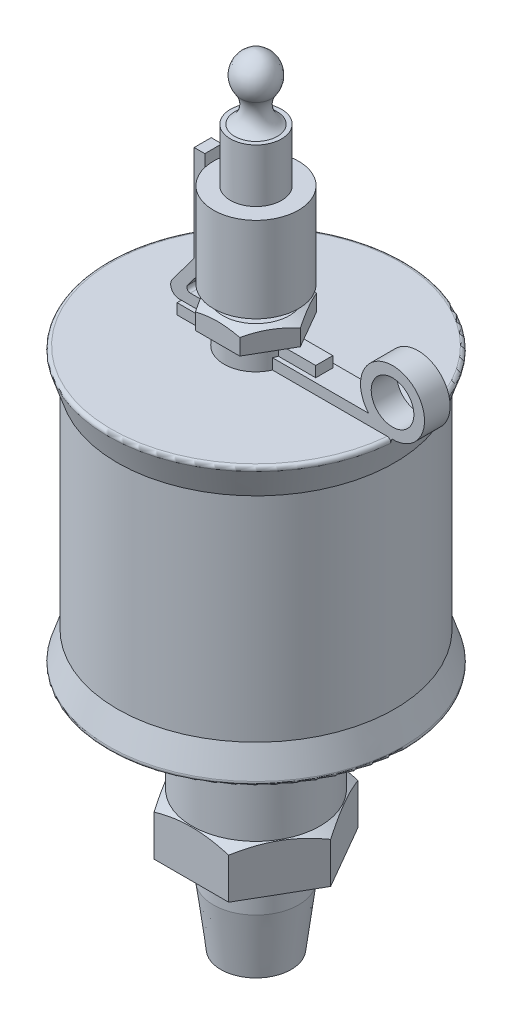
SolidWorks part; units mm, degrees
material "Plastic"
ref_plane "Front Plane" through (0, 0, 0) normal (0, 0, 1) x (1, 0, 0)
ref_plane "Top Plane" through (0, 0, 0) normal (0, 1, 0) x (1, 0, 0)
ref_plane "Right Plane" through (0, 0, 0) normal (1, 0, 0) x (0, 0, -1)
sketch "Sketch1" plane through (0, 0, 0) normal (0, 1, 0) x (1, 0, 0)
  circle A0 centre (0, 0) radius 22.225
  dimension "D1" = 44.45
extrude "Boss-Extrude1" add sketch "Sketch1" along normal mid plane 41.275
sketch "Sketch2" plane through (0, 0, 0) normal (0, 0, 1) x (1, 0, 0)
  line L0 (0, 21.5772) -> (0, -49978.4228) construction
  line L2 (-19.7921, 0) -> (49980.2079, 0) construction
  line L3 (20.6375, 15.875) -> (30.5336, 15.875)
  line L4 (20.6375, 15.875) -> (20.6375, -15.875)
  line L5 (20.6375, -15.875) -> (30.5336, -15.875)
  line L6 (30.5336, 15.875) -> (30.5336, -15.875)
  dimension "D1" = 41.275
  dimension "D2" = 31.75
revolve "Cut-Revolve1" cut sketch "Sketch2" angle 360 about L0
sketch "Sketch3" plane through (0, 0, 0) normal (0, 0, 1) x (1, 0, 0)
  line L0 (22.225, 20.6375) -> (20.6375, 15.875)
  line L1 (20.6375, 15.875) -> (22.225, 15.875)
  line L2 (22.225, 15.875) -> (22.225, 20.6375)
  line L3 (-22.6593, 0) -> (49977.3407, 0) construction
  line L5 (20.6375, -15.875) -> (22.225, -15.875)
  line L6 (22.225, -15.875) -> (22.225, -20.6375)
  line L7 (22.225, -20.6375) -> (20.6375, -15.875)
  line L8 (0, 12.3736) -> (0, -49987.6264) construction
revolve "Cut-Revolve2" cut sketch "Sketch3" angle 360 about L8
sketch "Sketch4" plane through (0, 0, 0) normal (0, 0, 1) x (1, 0, 0)
  line L0 (-10.3187, -20.6375) -> (0, -20.6375)
  line L1 (-22.225, -20.6375) -> (22.225, -20.6375) construction
  line L3 (0, -26.9875) -> (-10.3187, -26.9875)
  line L4 (-10.3187, -26.9875) -> (-10.3187, -20.6375)
  line L5 (0, 4.8841) -> (0, -49995.1159) construction
  line L7 (0, -20.6375) -> (0, -26.9875)
  dimension "D1" = 6.35
  dimension "D2" = 20.6375
revolve "Revolve2" add sketch "Sketch4" angle 360 about L5
sketch "Sketch5" plane through (0, 0, 0) normal (0, 0, 1) x (1, 0, 0)
  line L0 (-9.525, -26.9875) -> (-9.525, -36.5125)
  line L1 (-10.3187, -26.9875) -> (10.3187, -26.9875) construction
  line L2 (-9.525, -36.5125) -> (0, -36.5125)
  line L3 (0, -36.5125) -> (0, -26.9875) construction
  line L4 (0, -26.9875) -> (-9.525, -26.9875)
  line L5 (0, -36.5125) -> (0, -26.9875)
  dimension "D1" = 19.05
  dimension "D2" = 9.525
revolve "Revolve3" add sketch "Sketch5" angle 360 about L3
sketch "Sketch6" plane through (0, -36.5125, 0) normal (0, -1, 0) x (1, 0, 0)
  line L1 (11.1125, 0) -> (5.5562, 9.6237)
  line L2 (5.5562, 9.6237) -> (-5.5563, 9.6237)
  line L3 (-5.5563, 9.6237) -> (-11.1125, 0)
  line L4 (-11.1125, 0) -> (-5.5563, -9.6237)
  line L5 (-5.5563, -9.6237) -> (5.5562, -9.6237)
  line L6 (5.5562, -9.6237) -> (11.1125, 0)
  circle A0 centre (0, 0) radius 9.6237 construction
  dimension "D1" = 11.1125
extrude "Boss-Extrude2" add sketch "Sketch6" along normal blind 6.985
sketch "Sketch11" plane through (0, 0, 0) normal (0, 0, 1) x (1, 0, 0)
  line L0 (9.525, -36.5125) -> (11.1125, -37.429)
  line L1 (11.1125, -36.5125) -> (5.5562, -36.5125) construction
  line L2 (11.1125, -43.4975) -> (11.1125, -36.5125) construction
  line L3 (11.1125, -37.429) -> (11.1125, -36.5125)
  line L4 (11.1125, -36.5125) -> (9.525, -36.5125)
  line L5 (0, -29.1033) -> (0, -50029.1033) construction
  dimension "D1" = 1.5875
  dimension "D2" = 30
revolve "Cut-Revolve4" cut sketch "Sketch11" angle 360 about L5
sketch "Sketch12" plane through (0, 0, 0) normal (0, 0, 1) x (1, 0, 0)
  line L0 (0, -43.4975) -> (6.35, -43.4975)
  line L1 (5.5562, -43.4975) -> (-5.5563, -43.4975) construction
  line L2 (6.35, -43.4975) -> (6.35, -48.26)
  line L3 (6.35, -48.26) -> (0, -48.26)
  line L4 (0, -24.4475) -> (0, 24.4475) construction
  line L5 (0, -48.26) -> (0, -43.4975) construction
  line L6 (0, -43.4975) -> (0, -48.26)
  dimension "D1" = 12.7
  dimension "D2" = 4.7625
revolve "Revolve4" add sketch "Sketch12" angle 360 about L5
sketch "Sketch13" plane through (0, 0, 0) normal (0, 0, 1) x (1, 0, 0)
  line L0 (0, -57.15) -> (5.2387, -57.15)
  line L1 (5.2387, -57.15) -> (6.35, -48.26)
  line L2 (6.35, -48.26) -> (0, -48.26)
  line L3 (-6.35, -48.26) -> (6.35, -48.26) construction
  line L4 (0, -48.26) -> (0, -57.15) construction
  line L5 (0, -57.15) -> (0, -48.26)
  dimension "D1" = 10.4775
  dimension "D2" = 8.89
revolve "Revolve5" add sketch "Sketch13" angle 360 about L4
sketch "Sketch16" plane through (0, 0, 0) normal (0, 0, 1) x (1, 0, 0)
  line L0 (-9.8425, 20.6375) -> (22.225, 20.6375)
  line L1 (22.225, 20.6375) -> (-22.225, 20.6375) construction
  line L2 (0, 15.9486) -> (0, 50015.9486) construction
  line L4 (-9.8425, 20.6375) -> (-9.8425, 22.225)
  line L5 (-9.8425, 22.225) -> (18.6752, 22.225)
  arc A0 (22.225, 20.6375) -> (18.6752, 22.225) centre (22.225, 25.4) ccw
  circle A1 centre (22.225, 25.4) radius 3.175
  dimension "D3" = 9.525
  dimension "D4" = 1.5875
  dimension "D1" = 9.8425
  dimension "D2" = 22.225
  dimension "D5" = 1.5875
extrude "Boss-Extrude3" add sketch "Sketch16" along normal mid plane 3.81
sketch "Sketch17" plane through (0, 0, 0) normal (0, 0, 1) x (1, 0, 0)
  line L0 (0, 31.4144) -> (0, -49968.5856) construction
  line L1 (-11.176, 24.257) -> (-7.9375, 28.575)
  line L2 (0, 22.225) -> (10.16, 22.225)
  line L3 (18.6752, 22.225) -> (-9.8425, 22.225) construction
  line L4 (-8.509, 23.8125) -> (10.16, 23.8125)
  line L5 (0, 22.225) -> (-10.16, 22.225)
  line L6 (-7.9375, 28.575) -> (-7.9375, 42.8625)
  line L7 (8.5725, 23.8125) -> (8.5725, 23.8125)
  line L8 (10.16, 23.8125) -> (10.16, 22.225)
  line L9 (0, 22.225) -> (-12.7, 22.225) construction
  line L10 (-8.9154, 24.6253) -> (-6.35, 28.0458)
  line L11 (-6.35, 28.0458) -> (-6.35, 42.8625)
  line L12 (-6.35, 42.8625) -> (-7.9375, 42.8625)
  line L13 (-12.7, 22.225) -> (-7.9375, 28.575) construction
  line L14 (10.16, 22.225) -> (10.16, 23.8125) construction
  line L15 (0, 23.8125) -> (-9.525, 23.8125) construction
  line L16 (0, 23.8125) -> (8.5725, 23.8125) construction
  line L17 (-9.525, 23.8125) -> (-6.35, 28.0458) construction
  arc A0 (-10.16, 22.225) -> (-11.176, 24.257) centre (-10.16, 23.495) cw
  arc A1 (-8.509, 23.8125) -> (-8.9154, 24.6253) centre (-8.509, 24.3205) cw
  point P20 (-12.7, 22.225)
  dimension "D2" = 1.27
  dimension "D8" = 0.508
  dimension "D1" = 10.16
  dimension "D3" = 12.7
  dimension "D4" = 6.35
  dimension "D5" = 4.7625
  dimension "D6" = 14.2875
  dimension "D7" = 1.5875
extrude "Boss-Extrude4" add sketch "Sketch17" along normal mid plane 2.54 contours L4 A1 L10 L11 L12 L6 L1 A0 L5 L2 L8 region at (-9.3178, 26.2368, 0)
sketch "Sketch18" plane through (0, 0, 0) normal (0, 0, 1) x (1, 0, 0)
  line L0 (0, 24.6317) -> (0, -49975.3683) construction
  line L1 (0, 33.6264) -> (0, -49966.3736) construction
  line L2 (-8.509, 23.8125) -> (10.16, 23.8125) construction
  line L4 (0, 23.8125) -> (4.7625, 23.8125)
  line L5 (0, 23.8125) -> (0, 20.6375)
  line L6 (0, 20.6375) -> (4.7625, 20.6375)
  line L7 (4.7625, 23.8125) -> (4.7625, 20.6375)
  line L8 (22.1432, 20.6375) -> (-22.225, 20.6375) construction
  dimension "D1" = 4.7625
revolve "Revolve8" add sketch "Sketch18" angle 360 about L0
sketch "Sketch19" plane through (0, 23.8125, 0) normal (0, 1, 0) x (1, 0, 0)
  line L1 (3.2996, 5.715) -> (-3.2996, 5.715)
  line L2 (-3.2996, 5.715) -> (-6.5991, 0)
  line L3 (-6.5991, 0) -> (-3.2996, -5.715)
  line L4 (-3.2996, -5.715) -> (3.2996, -5.715)
  line L5 (3.2996, -5.715) -> (6.5991, 0)
  line L6 (6.5991, 0) -> (3.2996, 5.715)
  circle A0 centre (0, 0) radius 5.715 construction
  dimension "D1" = 11.43
extrude "Boss-Extrude5" add sketch "Sketch19" along normal blind 3.175
sketch "Sketch20" plane through (0, 0, 0) normal (0, 0, 1) x (1, 0, 0)
  line L0 (4.9493, 26.9875) -> (6.5991, 26.2193)
  line L1 (3.2996, 26.9875) -> (6.5991, 26.9875) construction
  line L2 (6.5991, 26.9875) -> (6.5991, 23.8125) construction
  line L3 (6.5991, 26.2193) -> (6.5991, 26.9875)
  line L4 (6.5991, 26.9875) -> (4.9493, 26.9875)
  line L5 (0, 32.0007) -> (0, -49967.9993) construction
revolve "Cut-Revolve5" cut sketch "Sketch20" angle 360 about L5
sketch "Sketch21" plane through (0, 26.9875, 0) normal (0, 1, 0) x (1, 0, 0)
  circle A0 centre (0, 0) radius 3.9688
  dimension "D1" = 7.9375
extrude "Boss-Extrude6" add sketch "Sketch21" along normal blind 1.5875
sketch "Sketch25" plane through (0, 0, 0) normal (0, 0, 1) x (1, 0, 0)
  line L0 (3.9688, 28.575) -> (-3.9688, 28.575) construction
  line L1 (0, 28.575) -> (-6.3246, 28.575)
  line L2 (0, 28.575) -> (0, 41.275)
  line L3 (0, 41.275) -> (-6.3246, 41.275)
  line L4 (-6.3246, 28.575) -> (-6.3246, 41.275)
  line L5 (0, -24.4475) -> (0, 24.4475) construction
  line L6 (0, 45.497) -> (0, -49954.503) construction
  dimension "D1" = 6.3246
  dimension "D2" = 12.7
revolve "Revolve14" add sketch "Sketch25" angle 360 about L6
sketch "Sketch26" plane through (0, 0, 0) normal (0, 0, 1) x (1, 0, 0)
  line L0 (6.3246, 41.275) -> (-6.3246, 41.275) construction
  line L1 (0, 41.275) -> (3.81, 41.275)
  line L2 (0, 41.275) -> (0, 49.2125) construction
  line L3 (0, 49.2125) -> (3.81, 49.2125)
  line L4 (3.81, 41.275) -> (3.81, 49.2125)
  line L5 (0, 41.275) -> (0, 49.2125)
  dimension "D1" = 3.81
  dimension "D2" = 7.9375
revolve "Revolve15" add sketch "Sketch26" angle 360 about L2
sketch "Sketch27" plane through (0, 0, 0) normal (0, 0, 1) x (1, 0, 0)
  line L0 (3.81, 49.2125) -> (-3.81, 49.2125) construction
  line L1 (0, -24.4475) -> (0, 24.4475) construction
  line L2 (0, 58.7375) -> (0, -49941.2625) construction
  line L3 (3.175, 49.2125) -> (0, 49.2125)
  line L4 (0, 58.7375) -> (0, 49.2125)
  arc A0 (3.175, 49.2125) -> (2.3052, 53.6211) centre (4.7359, 51.8106) cw
  arc A1 (2.3052, 53.6211) -> (0, 58.7375) centre (-0.2693, 55.5387) ccw
  dimension "D1" = 9.525
  dimension "D2" = 3.175
revolve "Revolve16" add sketch "Sketch27" angle 360 about L2
fillet "Fillet1" radius 0.508 2 edges at (0, -20.6375, 22.225) (-22.225, 20.6375, 0)
